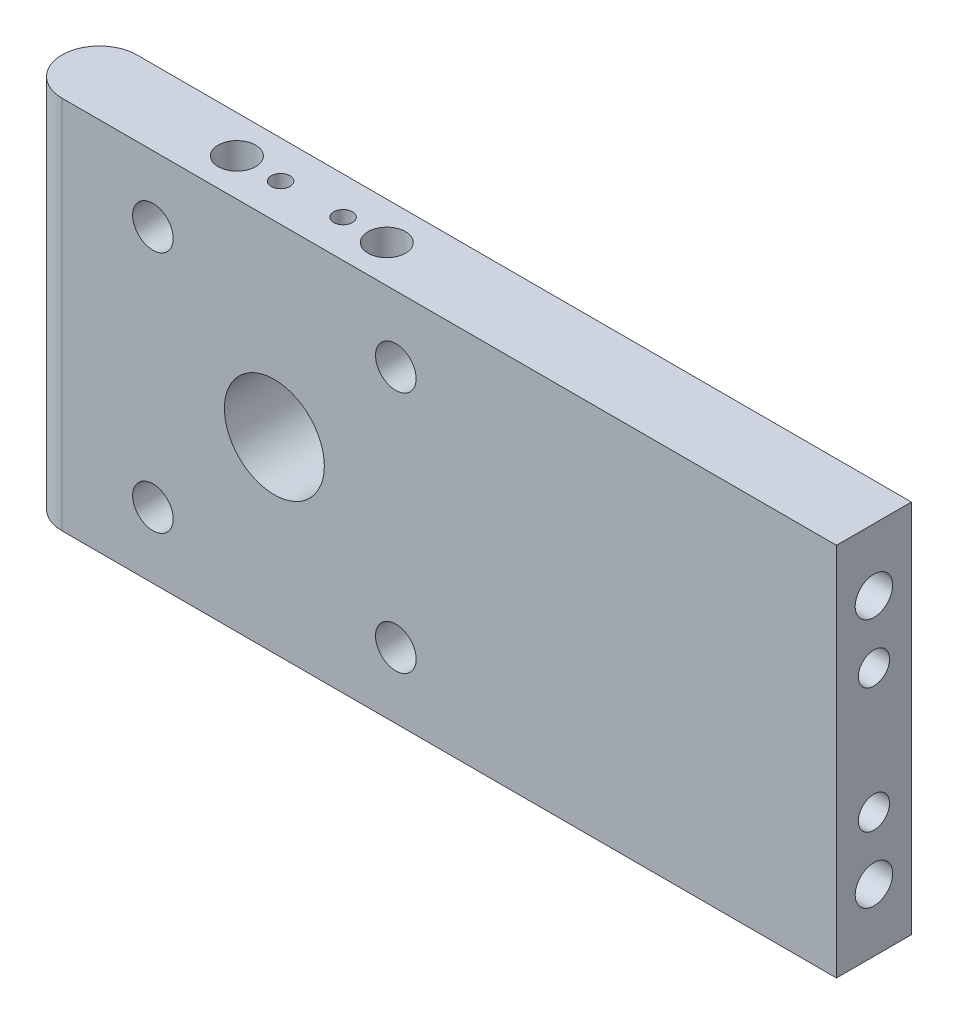
SolidWorks part; units mm, degrees
ref_plane "Front Plane" through (0, 0, 0) normal (0, 0, 1) x (1, 0, 0)
ref_plane "Top Plane" through (0, 0, 0) normal (0, 1, 0) x (1, 0, 0)
ref_plane "Right Plane" through (0, 0, 0) normal (1, 0, 0) x (0, 0, -1)
sketch "Sketch1" plane through (0, 0, 0) normal (0, 0, 1) x (1, 0, 0)
  line L0 (-25, 0) -> (-25, 27.5) construction
  line L1 (-65, -30) -> (65, -30)
  line L2 (-65, -30) -> (-65, 30)
  line L3 (-65, 30) -> (65, 30)
  line L4 (65, -30) -> (65, 30)
  line L5 (-65, -30) -> (65, 30) construction
  line L6 (-65, 30) -> (65, -30) construction
  line L7 (-25, 0) -> (-5.5546, 19.4454) construction
  line L8 (-25, 0) -> (-44.4454, 19.4454) construction
  line L9 (-25, 0) -> (65, 0) construction
  circle A0 centre (-25, 0) radius 8
  circle A1 centre (-25, 0) radius 27.5 construction
  circle A2 centre (-5.5546, 19.4454) radius 3.25
  circle A3 centre (-44.4454, 19.4454) radius 3.25
  circle A4 centre (-44.4454, -19.4454) radius 3.25
  circle A5 centre (-5.5546, -19.4454) radius 3.25
  point P0 (0, 0)
  point P19 (-65, 0)
  dimension "D3" = 55
  dimension "D4" = 16
  dimension "D7" = 6.5
  dimension "D8" = 6.5
  dimension "D1" = 60
  dimension "D2" = 130
  dimension "D5" = 45
  dimension "D6" = 45
  dimension "D9" = 40
extrude "Boss-Extrude1" add sketch "Sketch1" along normal blind 12
fillet "Fillet1" radius 6 2 edges at (-65, 0, 0) (-65, 0, 12)
sketch "Sketch2" plane through (65, 0, 0) normal (1, 0, 0) x (0, 0, -1)
  line L0 (0, 0) -> (-12, 0) construction
  line L1 (-12, -30) -> (-12, 30) construction
  line L2 (-6, 0) -> (-6, 4.4744) construction
  circle A0 centre (-6, 20) radius 3
  circle A1 centre (-6, 10) radius 2.5
  circle A2 centre (-6, -10) radius 2.5
  circle A3 centre (-6, -20) radius 3
  point P11 (-70.4794, 14.9413)
  dimension "D3" = 6
  dimension "D4" = 5
extrude "Cut-Extrude1" cut sketch "Sketch2" against normal blind 20
sketch "Sketch3" plane through (0, 30, 0) normal (0, 1, 0) x (1, 0, 0)
  line L0 (-25, 0) -> (-25, -12) construction
  line L1 (65, 0) -> (-59, 0) construction
  line L2 (65, -12) -> (-59, -12) construction
  line L3 (65, -12) -> (65, 0) construction
  circle A0 centre (-13, -6) radius 3
  circle A1 centre (-20, -6) radius 1.5
  circle A2 centre (-30, -6) radius 1.5
  circle A3 centre (-37, -6) radius 3
  dimension "D2" = 6
  dimension "D3" = 3
  dimension "D1" = 90
  dimension "D4" = 5
  dimension "D5" = 12
extrude "Cut-Extrude2" cut sketch "Sketch3" against normal blind 15
